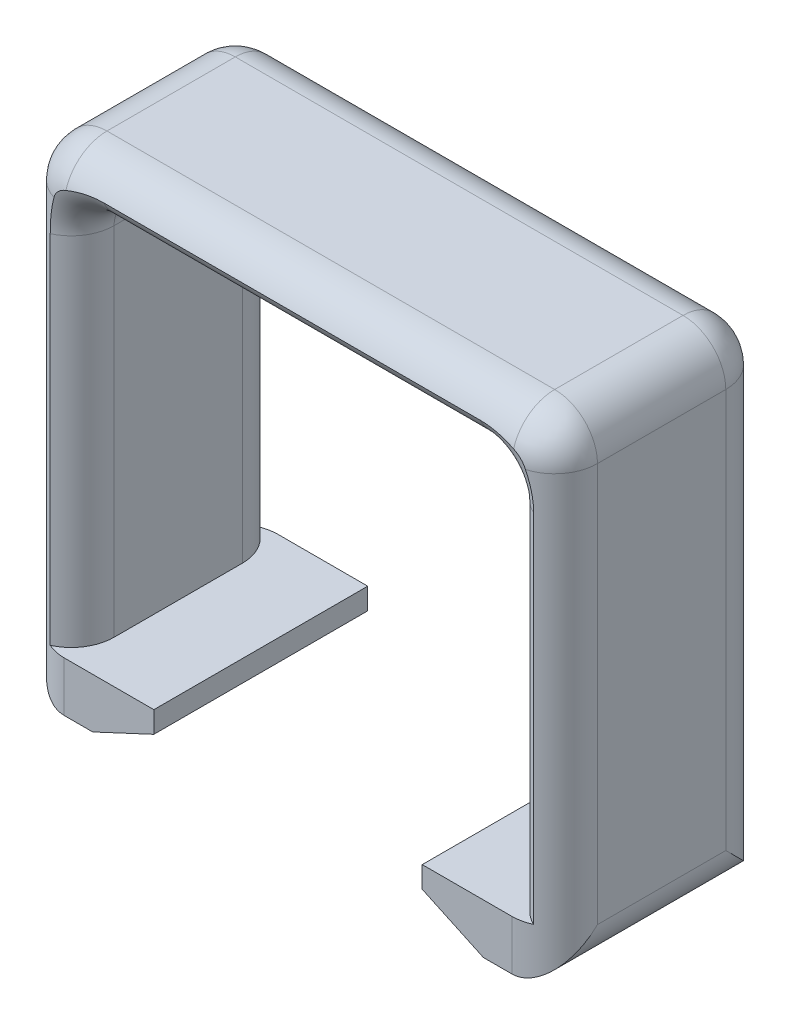
SolidWorks part; units mm, degrees
ref_plane "Front Plane" through (0, 0, 0) normal (0, 0, 1) x (1, 0, 0)
ref_plane "Top Plane" through (0, 0, 0) normal (0, 1, 0) x (1, 0, 0)
ref_plane "Right Plane" through (0, 0, 0) normal (1, 0, 0) x (0, 0, -1)
sketch "Sketch1" plane through (0, 0, 0) normal (0, 0, 1) x (1, 0, 0)
  line L0 (23.2876, 29.6675) -> (8.0876, 29.6675)
  line L1 (8.0876, 29.6675) -> (8.0876, 2.6675)
  line L3 (8.0876, 2.6675) -> (13.8766, 2.6675)
  line L4 (13.8766, 2.6675) -> (13.8766, 1.1675)
  line L5 (13.8766, 1.1675) -> (9.5876, -0.8325)
  line L6 (9.5876, -0.8325) -> (4.5876, -0.8325)
  line L7 (4.5876, -0.8325) -> (4.5876, 33.1675)
  line L8 (4.5876, 33.1675) -> (23.2876, 33.1675)
  line L9 (23.2876, 33.1675) -> (23.2876, 29.6675)
  point P2 (0, 0)
  dimension "D1" = 3.5
  dimension "D2" = 3.5
  dimension "D3" = 3.5
  dimension "D4" = 34
  dimension "D5" = 18.7
  dimension "D6" = 5
  dimension "D7" = 1.5
  dimension "D8" = 155
extrude "Boss-Extrude1" add sketch "Sketch1" against normal blind 15
mirror "Mirror1" about plane through (23.2876, 33.1675, -15) normal (1, 0, 0) of "Boss-Extrude1"
fillet "Fillet2" radius 3 10 edges at (41.9876, 16.1675, -15) (41.9876, -0.8325, -7.5) (41.9876, 16.1675, 0) (4.5876, -0.8325, -7.5) (4.5876, 16.1675, -15) (4.5876, 16.1675, 0) (4.5876, 33.1675, -7.5) (23.2876, 33.1675, -15) (41.9876, 33.1675, -7.5) (23.2876, 33.1675, 0)
fillet "Fillet3" radius 2 2 edges at (38.4876, 29.6675, -7.5) (8.0876, 29.6675, -7.5)
fillet "Fillet4" radius 3 10 edges at (8.0876, 15.1675, -15) (8.6734, 29.0817, -15) (37.9018, 29.0817, -15) (38.4876, 15.1675, -15) (38.4876, 15.1675, 0) (37.9018, 29.0817, 0) (8.6734, 29.0817, 0) (8.0876, 15.1675, 0) (23.2876, 29.6675, -15) (23.2876, 29.6675, 0)
